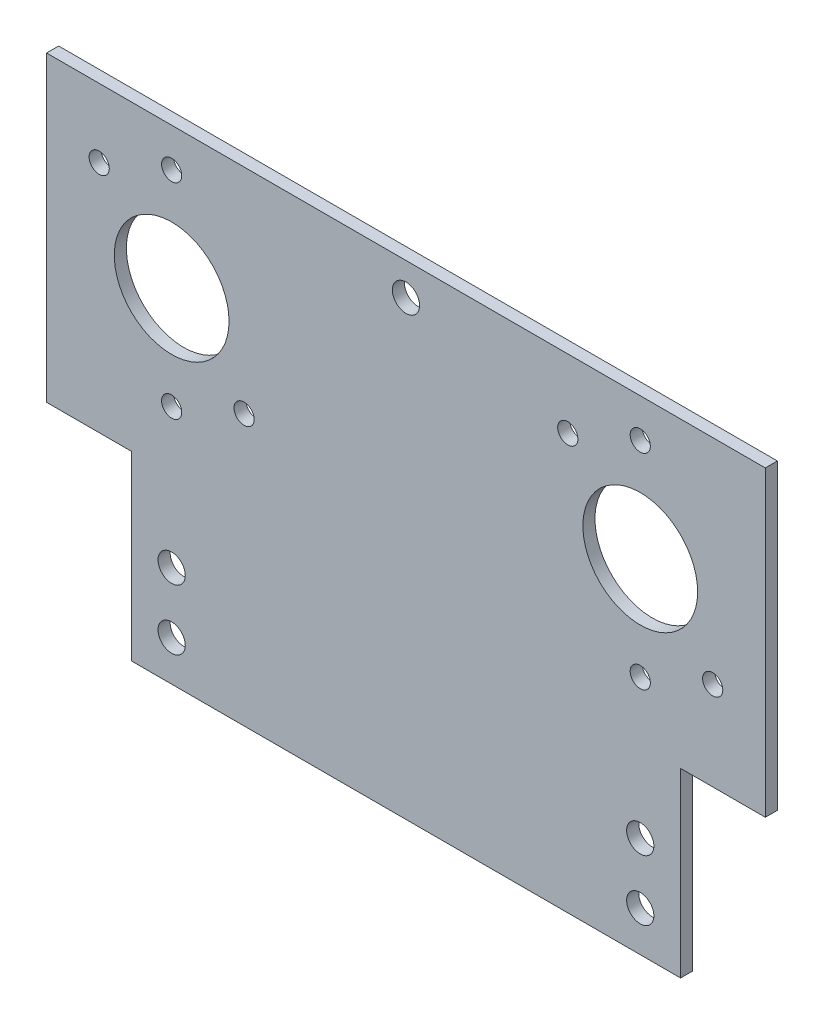
SolidWorks part; units mm, degrees
ref_plane "Front Plane" through (0, 0, 0) normal (0, 0, 1) x (1, 0, 0)
ref_plane "Top Plane" through (0, 0, 0) normal (0, 1, 0) x (1, 0, 0)
ref_plane "Right Plane" through (0, 0, 0) normal (1, 0, 0) x (0, 0, -1)
sketch "Sketch1" plane through (0, 0, 0) normal (0, 0, 1) x (1, 0, 0)
  line L1 (0, 0) -> (178.16, 0)
  line L2 (0, 0) -> (0, -120)
  line L3 (0, -120) -> (178.16, -120)
  line L4 (178.16, 0) -> (178.16, -120)
  dimension "D1" = 120
  dimension "D2" = 178.16
extrude "Boss-Extrude1" add sketch "Sketch1" along normal blind 3
sketch "Sketch2" plane through (0, 0, 3) normal (0, 0, 1) x (1, 0, 0)
  line L0 (0, 0) -> (0, -120) construction
  line L1 (178.16, -120) -> (178.16, 0) construction
  line L2 (0, -120) -> (178.16, -120) construction
  line L3 (178.16, 0) -> (0, 0) construction
  circle A0 centre (31, -35) radius 14.225
  circle A1 centre (147.16, -35) radius 14.225
  circle A2 centre (31, -110) radius 3.375
  circle A5 centre (147.16, -110) radius 3.375
  circle A7 centre (89.08, -8) radius 3.375
  circle A8 centre (31, -95) radius 3.375
  circle A9 centre (147.16, -95) radius 3.375
  point P9 (89.08, 0)
  dimension "D1" = 28.45
  dimension "D2" = 28.45
  dimension "D3" = 6.75
  dimension "D4" = 35
  dimension "D5" = 6.75
  dimension "D7" = 15
  dimension "D8" = 6.75
  dimension "D9" = 31
  dimension "D10" = 31
  dimension "D13" = 15
  dimension "D14" = 10
  dimension "D16" = 8
extrude "Cut-Extrude1" cut sketch "Sketch2" against normal through all
sketch "Sketch3" plane through (0, 0, 0) normal (0, 0, -1) x (-1, 0, 0)
  circle A0 centre (-48.9605, -52.9605) radius 2.0193 construction
  circle A1 centre (-31, -9.6) radius 2.0193 construction
  circle A2 centre (-13.0395, -17.0395) radius 2.0193 construction
  circle A3 centre (-48.9605, -52.9605) radius 2.0193
  circle A4 centre (-31, -9.6) radius 2.0193
  circle A5 centre (-13.0395, -17.0395) radius 2.0193
  circle A6 centre (-31, -60.4) radius 2.0193 construction
  circle A7 centre (-31, -60.4) radius 2.0193
  circle A8 centre (-129.1995, -17.0395) radius 2.0193 construction
  circle A9 centre (-147.16, -9.6) radius 2.0193 construction
  circle A10 centre (-129.1995, -17.0395) radius 2.0193
  circle A11 centre (-147.16, -9.6) radius 2.0193
  circle A12 centre (-147.16, -60.4) radius 2.0193 construction
  circle A13 centre (-165.1205, -52.9605) radius 2.0193 construction
  circle A14 centre (-147.16, -60.4) radius 2.0193
  circle A15 centre (-165.1205, -52.9605) radius 2.0193
  point P25 (-31, -60.4)
  point P26 (-48.9605, -52.9605)
  point P27 (-31, -9.6)
  point P28 (-13.0395, -17.0395)
  point P29 (-147.16, -60.4)
  point P30 (-165.1205, -52.9605)
  point P31 (-147.16, -9.6)
  point P32 (-129.1995, -17.0395)
extrude "Cut-Extrude2" cut sketch "Sketch3" against normal through all
sketch "Sketch6" plane through (0, 0, 3) normal (0, 0, 1) x (1, 0, 0)
  circle A0 centre (31, -60.4) radius 2.5
  circle A1 centre (48.9605, -52.9605) radius 2.5
  circle A3 centre (31, -9.6) radius 2.5
  circle A4 centre (13.0395, -17.0395) radius 2.5
  circle A5 centre (165.1205, -52.9605) radius 2.5
  circle A6 centre (147.16, -60.4) radius 2.5
  circle A7 centre (129.1995, -17.0395) radius 2.5
  circle A8 centre (147.16, -9.6) radius 2.5
  dimension "D1" = 5
  dimension "D2" = 5
  dimension "D3" = 5
  dimension "D4" = 5
  dimension "D5" = 5
  dimension "D6" = 5
  dimension "D7" = 5
  dimension "D8" = 5
extrude "Cut-Extrude3" cut sketch "Sketch6" against normal through all
sketch "Sketch7" plane through (0, 0, 3) normal (0, 0, 1) x (1, 0, 0)
  line L1 (178.16, -120) -> (157.16, -120)
  line L2 (178.16, -120) -> (178.16, -75)
  line L3 (178.16, -75) -> (157.16, -75)
  line L4 (157.16, -120) -> (157.16, -75)
  line L5 (0, -120) -> (21, -120)
  line L6 (0, -120) -> (0, -75)
  line L7 (0, -75) -> (21, -75)
  line L8 (21, -120) -> (21, -75)
  dimension "D1" = 21
  dimension "D2" = 21
  dimension "D3" = 45
  dimension "D4" = 45
extrude "Cut-Extrude4" cut sketch "Sketch7" against normal through all
